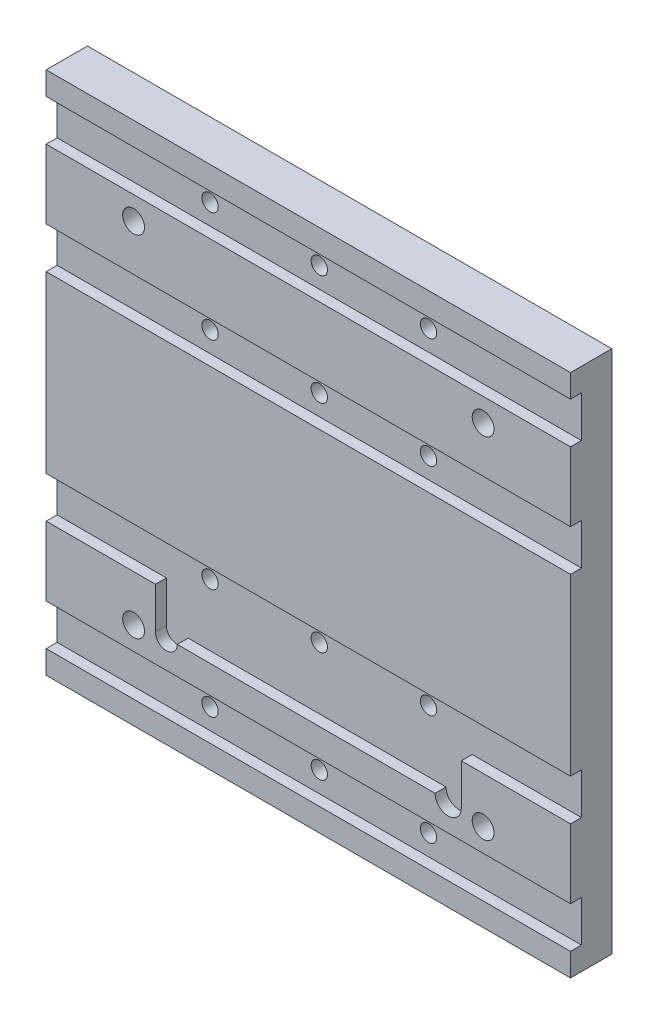
SolidWorks part; units mm, degrees
material "Acrylic (Medium-high impact)"
ref_plane "Front Plane" through (0, 0, 0) normal (0, 0, 1) x (1, 0, 0)
ref_plane "Top Plane" through (0, 0, 0) normal (0, 1, 0) x (1, 0, 0)
ref_plane "Right Plane" through (0, 0, 0) normal (1, 0, 0) x (0, 0, -1)
sketch "Sketch1" plane through (0, 0, 0) normal (0, 0, 1) x (1, 0, 0)
  line L1 (-76.2, 76.2) -> (76.2, 76.2)
  line L2 (-76.2, 76.2) -> (-76.2, -76.2)
  line L3 (-76.2, -76.2) -> (76.2, -76.2)
  line L4 (76.2, 76.2) -> (76.2, -76.2)
  line L5 (-76.2, 76.2) -> (76.2, -76.2) construction
  line L6 (-76.2, -76.2) -> (76.2, 76.2) construction
  circle A0 centre (-50.8, 50.8) radius 3.175
  circle A1 centre (-50.8, -50.8) radius 3.175
  circle A2 centre (50.8, 50.8) radius 3.175
  circle A3 centre (50.8, -50.8) radius 3.175
  point P0 (0, 0)
  dimension "D5" = 6.35
  dimension "D6" = 6.35
  dimension "D7" = 6.35
  dimension "D8" = 6.35
  dimension "D9" = 25.4
  dimension "D10" = 25.4
  dimension "D11" = 25.4
  dimension "D12" = 25.4
  dimension "D13" = 25.4
  dimension "D14" = 25.4
  dimension "D15" = 25.4
  dimension "D16" = 101.6
  dimension "D1" = 0
  dimension "D2" = 0
  dimension "D3" = 152.4
  dimension "D4" = 152.4
extrude "Boss-Extrude1" add sketch "Sketch1" along normal blind 12
sketch "Sketch2" plane through (0, 0, 12) normal (0, 0, 1) x (1, 0, 0)
  line L0 (76.2, -76.2) -> (76.2, 76.2) construction
  line L1 (-76.2, -25.4) -> (76.2, -25.4)
  line L2 (-76.2, -25.4) -> (-76.2, -37.4)
  line L3 (-76.2, -37.4) -> (76.2, -37.4) construction
  line L4 (76.2, -25.4) -> (76.2, -37.4)
  line L5 (-76.2, -25.4) -> (76.2, -37.4) construction
  line L6 (-76.2, -37.4) -> (76.2, -25.4) construction
  line L7 (-76.2, 37.4) -> (76.2, 37.4)
  line L8 (-76.2, 37.4) -> (-76.2, 25.4)
  line L9 (-76.2, 25.4) -> (76.2, 25.4)
  line L10 (76.2, 37.4) -> (76.2, 25.4)
  line L11 (-76.2, 37.4) -> (76.2, 25.4) construction
  line L12 (-76.2, 25.4) -> (76.2, 37.4) construction
  line L13 (-76.2, 69.5) -> (76.2, 69.5)
  line L14 (-76.2, 69.5) -> (-76.2, 57.5)
  line L15 (-76.2, 57.5) -> (76.2, 57.5)
  line L16 (76.2, 69.5) -> (76.2, 57.5)
  line L17 (-76.2, 69.5) -> (76.2, 57.5) construction
  line L18 (-76.2, 57.5) -> (76.2, 69.5) construction
  line L19 (-76.2, -57.5) -> (76.2, -57.5)
  line L20 (-76.2, -57.5) -> (-76.2, -69.5)
  line L21 (-76.2, -69.5) -> (76.2, -69.5)
  line L22 (76.2, -57.5) -> (76.2, -69.5)
  line L23 (-76.2, -57.5) -> (76.2, -69.5) construction
  line L24 (-76.2, -69.5) -> (76.2, -57.5) construction
  line L25 (-76.2, -76.2) -> (76.2, -76.2) construction
  line L26 (76.2, 76.2) -> (-76.2, 76.2) construction
  line L27 (-76.2, 76.2) -> (-76.2, -76.2) construction
  line L28 (76.2, -37.4) -> (44.45, -37.4)
  line L29 (44.45, -37.4) -> (-44.45, -37.4) construction
  line L30 (44.45, -37.4) -> (44.45, -49.3888)
  line L31 (44.45, -49.3888) -> (-44.45, -49.3888) construction
  line L32 (-44.45, -37.4) -> (-44.45, -49.3888)
  line L33 (-44.45, -37.4) -> (-76.2, -37.4)
  line L34 (-38.1, -49.3888) -> (36.83, -49.3888)
  circle A0 centre (-31.75, 63.5) radius 2.3812
  circle A1 centre (0, 63.5) radius 2.3812
  circle A2 centre (0, -63.5) radius 2.3813
  circle A3 centre (0, -31.4) radius 2.3813
  circle A4 centre (0, 31.4) radius 2.3812
  circle A5 centre (31.75, 31.4) radius 2.3812
  circle A6 centre (-31.75, 31.4) radius 2.3812
  circle A7 centre (31.75, 63.5) radius 2.3812
  circle A8 centre (-31.75, -63.5) radius 2.3812
  circle A9 centre (31.75, -63.5) radius 2.3812
  circle A10 centre (-31.75, -31.4) radius 2.3812
  circle A11 centre (31.75, -31.4) radius 2.3812
  arc A12 (44.45, -49.3888) -> (36.83, -49.3888) centre (40.64, -49.3888) cw
  arc A13 (-44.45, -49.3888) -> (-38.1, -49.3888) centre (-41.275, -49.3888) ccw
  point P0 (0, -31.4)
  point P5 (0, 31.4)
  point P10 (0, 63.5)
  point P15 (0, -63.5)
  point P56 (0, -49.3888)
  dimension "D18" = 4.7625
  dimension "D19" = 4.7625
  dimension "D20" = 4.7625
  dimension "D21" = 4.7625
  dimension "D22" = 4.7625
  dimension "D23" = 4.7625
  dimension "D24" = 4.7625
  dimension "D25" = 4.7625
  dimension "D28" = 4.7625
  dimension "D31" = 4.7625
  dimension "D17" = 31.75
  dimension "D32" = 31.75
  dimension "D35" = 31.75
  dimension "D37" = 0
  dimension "D40" = 4.7625
  dimension "D41" = 4.7625
  dimension "D45" = 6
  dimension "D46" = 6
  dimension "D49" = 3.81
  dimension "D50" = 3.175
  dimension "D1" = 152.4
  dimension "D2" = 12
  dimension "D3" = 0
  dimension "D4" = 152.4
  dimension "D5" = 12
  dimension "D6" = 12.7
  dimension "D7" = 12.7
  dimension "D8" = 0
  dimension "D9" = 152.4
  dimension "D10" = 0
  dimension "D11" = 12
  dimension "D12" = 50.8
  dimension "D13" = 152.4
  dimension "D14" = 12
  dimension "D15" = 50.8
  dimension "D16" = 0
  dimension "D26" = 0
  dimension "D27" = 0
  dimension "D29" = 0
  dimension "D30" = 0
  dimension "D33" = 0
  dimension "D34" = 31.75
  dimension "D36" = 0
  dimension "D38" = 31.75
  dimension "D39" = 31.75
  dimension "D42" = 31.75
  dimension "D43" = 31.75
  dimension "D44" = 6
  dimension "D47" = 11.9888
  dimension "D48" = 88.9
extrude "Cut-Extrude1" cut sketch "Sketch2" against normal blind 3.175
sketch "Sketch3" plane through (0, 0, 12) normal (0, 0, 1) x (1, 0, 0)
  circle A0 centre (-31.75, 63.5) radius 2.3813
  circle A1 centre (0, 63.5) radius 2.3813
  circle A2 centre (31.75, 63.5) radius 2.3812
  circle A3 centre (-31.75, 31.4) radius 2.3812
  circle A4 centre (0, 31.4) radius 2.3813
  circle A5 centre (31.75, 31.4) radius 2.3813
  circle A6 centre (-31.75, -31.4) radius 2.3812
  circle A7 centre (0, -31.4) radius 2.3813
  circle A8 centre (31.75, -31.4) radius 2.3813
  circle A9 centre (-31.75, -63.5) radius 2.3812
  circle A10 centre (0, -63.5) radius 2.3813
  circle A11 centre (31.75, -63.5) radius 2.3812
extrude "Cut-Extrude2" cut sketch "Sketch3" against normal through all
sketch "Sketch5" plane through (0, 0, 0) normal (0, 0, -1) x (-1, 0, 0)
  circle A0 centre (31.75, -63.5) radius 3.9687
  circle A1 centre (0, -63.5) radius 3.9688
  circle A2 centre (-31.75, -63.5) radius 3.9688
  circle A3 centre (-31.75, -31.4) radius 3.9688
  circle A4 centre (0, -31.4) radius 3.9688
  circle A5 centre (31.75, -31.4) radius 3.9687
  circle A6 centre (31.75, 31.4) radius 3.9687
  circle A7 centre (0, 31.4) radius 3.9688
  circle A8 centre (-31.75, 31.4) radius 3.9688
  circle A9 centre (-31.75, 63.5) radius 3.9688
  circle A10 centre (0, 63.5) radius 3.9687
  circle A11 centre (31.75, 63.5) radius 3.9687
  dimension "D1" = 7.9375
  dimension "D2" = 7.9375
  dimension "D3" = 7.9375
  dimension "D4" = 7.9375
  dimension "D5" = 7.9375
  dimension "D6" = 7.9375
  dimension "D7" = 7.9375
  dimension "D8" = 7.9375
  dimension "D9" = 7.9375
  dimension "D10" = 7.9375
  dimension "D11" = 7.9375
  dimension "D12" = 7.9375
extrude "Cut-Extrude7" cut sketch "Sketch5" against normal blind 5.08
